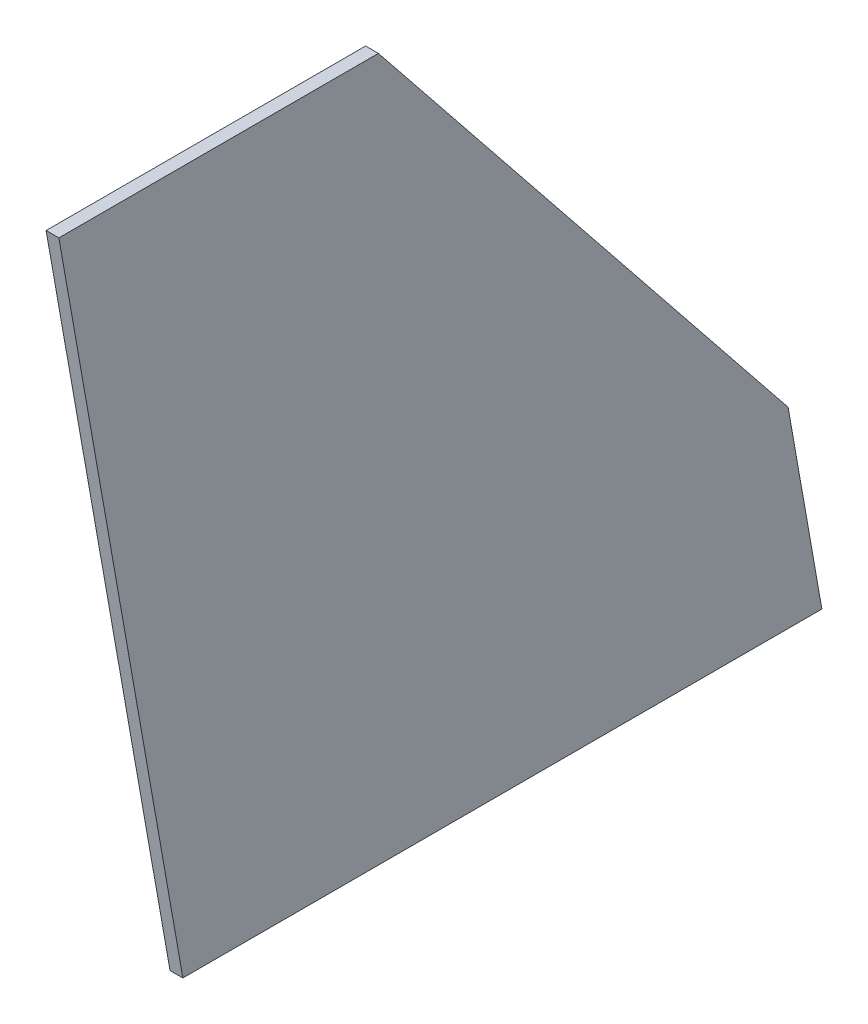
SolidWorks part; units mm, degrees
material "Thornel Mat VMA"
ref_plane "Front Plane" through (0, 0, 0) normal (0, 0, 1) x (1, 0, 0)
ref_plane "Top Plane" through (0, 0, 0) normal (0, 1, 0) x (1, 0, 0)
ref_plane "Right Plane" through (0, 0, 0) normal (1, 0, 0) x (0, 0, -1)
other "Center of Mass"
sketch "Sketch1" plane through (0, 0, 0) normal (1, 0, 0) x (0, 0, -1)
  line L0 (0, 0) -> (127, 0)
  line L1 (127, 0) -> (120.2819, 38.1)
  line L2 (120.2819, 38.1) -> (38.8671, 139.7)
  line L3 (38.8671, 139.7) -> (-24.6329, 139.7)
  line L4 (-24.6329, 139.7) -> (0, 0)
  dimension "D1" = 139.7
  dimension "D2" = 127
  dimension "D3" = 80
  dimension "D4" = 38.1
  dimension "D5" = 100
  dimension "D6" = 63.5
extrude "Boss-Extrude1" add sketch "Sketch1" along normal blind 1.27 and the other way blind 1.27 contours L4 L0 L1 L2 L3
